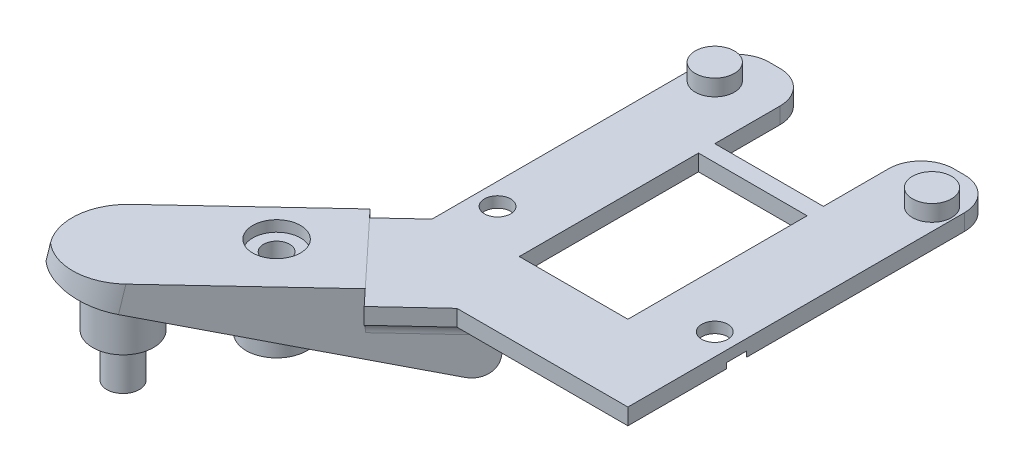
SolidWorks part; units mm, degrees
material "ABS"
ref_plane "Plan de face" through (0, 0, 0) normal (0, 0, 1) x (1, 0, 0)
ref_plane "Plan de dessus" through (0, 0, 0) normal (0, 1, 0) x (1, 0, 0)
ref_plane "Plan de droite" through (0, 0, 0) normal (1, 0, 0) x (0, 0, -1)
sketch "Esquisse1" plane through (0, 0, 0) normal (0, 1, 0) x (1, 0, 0)
  line L1 (-12, -19) -> (12, -19)
  line L2 (-12, -19) -> (-12, 19)
  line L3 (-12, 19) -> (12, 19)
  line L4 (12, -19) -> (12, 19)
  line L5 (-12, -19) -> (12, 19) construction
  line L6 (-12, 19) -> (12, -19) construction
  line L11 (-5, -12) -> (5, -12)
  line L12 (0, 2.75) -> (0, 0) construction
  line L13 (-5, -12) -> (-5, 17.5)
  line L14 (-5, 17.5) -> (5, 17.5)
  line L15 (5, -12) -> (5, 17.5)
  line L16 (-5, -12) -> (5, 17.5) construction
  line L17 (-5, 17.5) -> (5, -12) construction
  point P0 (0, 0)
  dimension "D1" = 24
  dimension "D2" = 38
  dimension "D3" = 1.5
  dimension "D4" = 7
  dimension "D5" = 7
extrude "Shape" add sketch "Esquisse1" along normal blind 1.5
sketch "Esquisse2" plane through (0, 1.5, 0) normal (0, 1, 0) x (1, 0, 0)
  line L0 (10, 19) -> (10, -19) construction
  line L1 (12, 19) -> (-12, 19) construction
  line L2 (-12, -19) -> (12, -19) construction
  line L3 (10, -19) -> (0, -19) construction
  circle A0 centre (10, -9) radius 1.2
  dimension "D2" = 2.4
  dimension "D3" = 10
extrude "VisHoles" cut sketch "Esquisse2" against normal blind 1.5
sketch "Esquisse3" plane through (0, 1.5, 0) normal (0, 1, 0) x (1, 0, 0)
  line L0 (12, 21) -> (-12, 21) construction
  line L1 (12, -19) -> (12, 19) construction
  line L2 (-12, 19) -> (-12, -19) construction
  line L3 (-12, -19) -> (12, -19) construction
  line L4 (0, 21) -> (0, -19) construction
  line L5 (10, -9) -> (10, 1) construction
  line L6 (0, 1) -> (10, 1) construction
  line L7 (10, 1) -> (10, 21) construction
  circle A0 centre (10, 11) radius 1.8
  line M6 (12, -19) -> (12, 19)
  dimension "D2" = 3.6
  dimension "D1" = 40
extrude "Lockers" add sketch "Esquisse3" along normal blind 1.5 contours A0 M6 region at (10, 1.5, -11)
sketch "Esquisse4" plane through (0, 0, 0) normal (0, 1, 0) x (1, 0, 0)
  circle A0 centre (10, -9) radius 2.2
  dimension "D1" = 4.4
extrude "ScrewHatRemover" cut sketch "Esquisse4" along normal blind 0.5
mirror "Symétrie1" about plane through (0, 0, 0) normal (1, 0, 0) of "ScrewHatRemover", "VisHoles", "Lockers"
sketch "Esquisse5" plane through (0, 1.5, 0) normal (0, 1, 0) x (1, 0, 0)
  line L0 (12, -19) -> (12, 19) construction
  line L9 (-12, 19) -> (12, 19)
  line L15 (-12, 19) -> (-12, 15)
  line L16 (-12, 15) -> (12, 15)
  line L17 (12, 19) -> (12, 15)
  dimension "D1" = 4
extrude "Enlèv. mat.-Extru.1" cut sketch "Esquisse5" against normal blind 10
sketch "Esquisse6" plane through (0, 1.5, 0) normal (0, 1, 0) x (1, 0, 0)
  line L0 (-5, 15) -> (-5, -12) construction
  line L1 (-5, 6) -> (5, 6)
  line L2 (-5, 6) -> (-5, 4.5)
  line L3 (-5, 4.5) -> (5, 4.5)
  line L4 (5, 6) -> (5, 4.5)
  line L5 (5, -12) -> (5, 15) construction
  circle A0 centre (-10, 11) radius 1.8 construction
  dimension "D1" = 1.5
  dimension "D2" = 5
extrude "Ribs" add sketch "Esquisse6" against normal up to surface (1.5 mm away) up to face at (0, 0, 3.1667)
fillet "Congé1" radius 3 4 edges at (-12, 0.75, -15) (-5, 0.75, -15) (5, 0.75, -15) (12, 0.75, -15)
sketch "Esquisse7" plane through (0, 1.5, 0) normal (0, 1, 0) x (1, 0, 0)
  line L0 (-12, -13.0327) -> (-14.9764, -15.8082)
  line L1 (-12, 12) -> (-12, -19) construction
  line L2 (-14.9764, -15.8082) -> (-8.1564, -23.1218)
  line L3 (-8.1564, -23.1218) -> (-3.7363, -19)
  line L4 (-3.7363, -19) -> (-12, -19)
  line L5 (-12, -19) -> (-12, -13.0327)
  line L6 (-12, -19) -> (12, -19) construction
  line M8 (-12, 12) -> (-12, -19)
  line M9 (-12, -19) -> (12, -19)
  dimension "D1" = 133
  dimension "D2" = 10
extrude "Angle" add sketch "Esquisse7" against normal up to surface (1.5 mm away) contours L2 L3 M9 | L0 L2 M8 region at (-12.9921, 1.5, 15.947) region at (-7.9642, 1.5, 20.3739) up to face at (0, 0, -3.0303)
sketch "Ref" plane through (0, 1.5, 0) normal (0, 1, 0) x (1, 0, 0)
  line L0 (-10, 11) -> (10, 11) construction
  line L1 (-11.5664, -19.465) -> (0, -8.6792) construction
  line L2 (-14.9764, -15.8082) -> (-8.1564, -23.1218) construction
  line L3 (0, -8.6792) -> (0, 11) construction
  line L4 (0, -8.6792) -> (16.5976, 6.7984) construction
  line L5 (0, 11) -> (9.8156, 0.474) construction
sketch3d "PlanSocle"
  line L0 (-11.5664, 1.5, 19.465) -> (0, 1.5, 8.6792) construction
sketch "Esquisse11" plane through (4.329, 0, 4.6423) normal (0.682, 0, 0.7314) x (0.7314, 0, -0.682)
  line L0 (7.502, 1.5) -> (7.502, -20.4) construction
  line L1 (7.502, -20.4) -> (7.502, -9.9) construction
  line L2 (7.502, -15.15) -> (-43.178, -15.15) construction
  line L3 (-43.178, -15.15) -> (-43.178, 0.1) construction
  line L4 (7.502, -9.9) -> (-43.178, 0.1) construction
  line L5 (-42.7135, 0.0083) -> (-13.281, -5.7992)
  line L6 (-13.281, -5.7992) -> (-11.8407, 1.5)
  line L7 (7.7488, 0) -> (11.8407, 0) construction
  line L8 (-42.7135, 0.0083) -> (-42.4231, 1.48)
  line L11 (-11.8407, 1.5) -> (-11.8407, 0)
  line L12 (-21.7342, 1.5) -> (-5.9192, 1.5) construction
  line L14 (-11.8407, 1.5) -> (-11.8407, 0) construction
  line L15 (-42.4231, 1.48) -> (-21.7342, 1.5)
  line L16 (-21.7342, 1.5) -> (-11.8407, 1.5)
  line L24 (30.4061, -15.15) -> (7.502, -15.15) construction
  dimension "D3" = 50.68
  dimension "D4" = 30
  dimension "D2" = 15.25
  dimension "D5" = 1.5
  dimension "D1" = 10.5
  dimension "D6" = 9.9
extrude "Socle" add sketch "Esquisse11" along normal blind 3 and the other way blind 4 contours L11 L6 L5 L8 | L16 L15 L8 L5 L6 region at (-13.4008, -1.0213, 21.1756)
sketch "Esquisse19" plane through (-0.5903, 0, 0.5505) normal (0, -1, 0) x (1, 0, 0.0095)
  line L0 (-6.3164, 11.4604) -> (-27.6497, 31.7376) construction
  line L1 (-7.424, 10.2952) -> (-2.6014, 15.369) construction
  line L2 (-28.7572, 30.5724) -> (-23.9347, 35.6462) construction
  line L3 (-23.9347, 35.6462) -> (-2.6014, 15.369) construction
  line L4 (0.4802, -11.5556) -> (-25.0335, 12.695) construction
  line L5 (-25.0335, 12.695) -> (-16.7662, 21.3929) construction
  line L6 (0.6678, 8.1227) -> (17.1171, -7.5123) construction
  line L7 (-16.7662, 21.3929) -> (8.7475, -2.8578) construction
  line L8 (0.4802, -11.5556) -> (10.3957, -1.1237) construction
  circle A0 centre (-16.7662, 21.3929) radius 1.2
  circle A1 centre (-24.0144, 28.2822) radius 1.5
  dimension "D2" = 2.4
  dimension "D3" = 10
  dimension "D5" = 3
  dimension "D1" = 12
  dimension "D4" = 35.2
extrude "ScrewHoles" cut sketch "Esquisse19" along normal through all and the other way blind 16 contours A0 | A0
extrude "ScrewPlot" add sketch "Esquisse19<3>" along normal blind 10 contours A1
sketch "Esquisse19<3>" plane through (-0.5903, 0, 0.5505) normal (0, -1, 0) x (1, 0, 0.0095) same geometry as "Esquisse19"
sketch "Esquisse20" plane through (1.601, 0, 1.7169) normal (-0.682, 0, -0.7314) x (-0.7314, 0, 0.682)
  line L0 (42.4231, 1.48) -> (42.7135, 0.0083)
  line L1 (42.7135, 0.0083) -> (18.6475, -4.7403)
  line L2 (42.7135, 0.0083) -> (13.281, -5.7992) construction
  line L3 (18.6475, -4.7403) -> (17.7122, 0)
  line L4 (17.6645, 0) -> (21.7342, 0) construction
  line L5 (17.7122, 0) -> (21.7342, 0)
  line L6 (21.7342, 0) -> (21.7342, 1.5)
  line L7 (21.7342, 1.5) -> (42.4231, 1.48)
  line L9 (12.1367, 0) -> (21.7342, 0) construction
extrude "ElargmentSurface" add sketch "Esquisse20" along normal blind 2
sketch "Esquisse26" plane through (0, 0, 0) normal (0, 1, 0) x (1, 0, 0)
  circle A0 centre (-17.5597, -21.7826) radius 2.8
  circle A1 centre (-24.8732, -28.6026) radius 2.8
  circle A2 centre (-17.5597, -21.7826) radius 1.2
  circle A3 centre (-17.5597, -21.7826) radius 1.2 construction
  dimension "D1" = 5.6
extrude "Flatten" add sketch "Esquisse26" against normal blind 6
sketch "Esquisse27" plane through (-0.0011, 1.521, 0.001) normal (-0.0007, 1, 0.0007) x (1, 0.0007, 0)
  circle A0 centre (-17.5586, -21.7816) radius 2.2
  dimension "D1" = 4.4
extrude "Enlèv. mat.-Extru.6" cut sketch "Esquisse27" against normal blind 1
fillet "Congé2" radius 5 3 edges at (-13.0589, -2.3701, 12.6528) (-24.7575, 0.7442, 35.8679) (-30.8955, 0.7442, 29.2857)
fillet "Congé3" radius 2 5 edges at (-6.0108, 0, 18.3863) (-9.314, 0, 11.8953) (-4.8882, 0, 12.5539) (-5.7251, -5.7992, 13.3342) (-10.0745, -5.2697, 12.6045)
equation "\"entretoiseBearing\"= 1.5mm"
equation "\"length_tibia\"= 206mm"
equation "\"length_femur\"= 117mm"
equation "\"length_coxa\"= 27mm"
equation "\"height\"= 40mm"
equation "\"width\"= 100mm"
equation "\"lever\"= 40mm"
equation "\"errorFlat\"= 0.20mm"
equation "\"errorFlat_tight\"= 0.15mm"
equation "\"errorCircle\"= 0.40mm"
equation "\"errorCircle_tight\" = 0.30mm"
equation "\"cuticule\"=1.5mm"
equation "\"cuticule_attach_w\"=10mm"
equation "\"cuticule_attach_h\"=2.5mm"
equation "\"depthMagnet\"= 1mm"
equation "\"insert_d\" = 3.2mm"
equation "\"insert_l\" = 5mm"
equation "\"D2@Esquisse2\"= 2.00mm + \"errorCircle\""
equation "\"D2@Esquisse3\"= 4 - \"errorCircle\""
equation "\"D1@Esquisse4\"=4 + \"errorCircle\""
equation "\"D5@Esquisse11\"= \"cuticule\""
equation "\"D2@Esquisse19\"= 2 + \"errorCircle\""
equation "\"D1@Esquisse26\"= 6 - \"errorCircle\""
